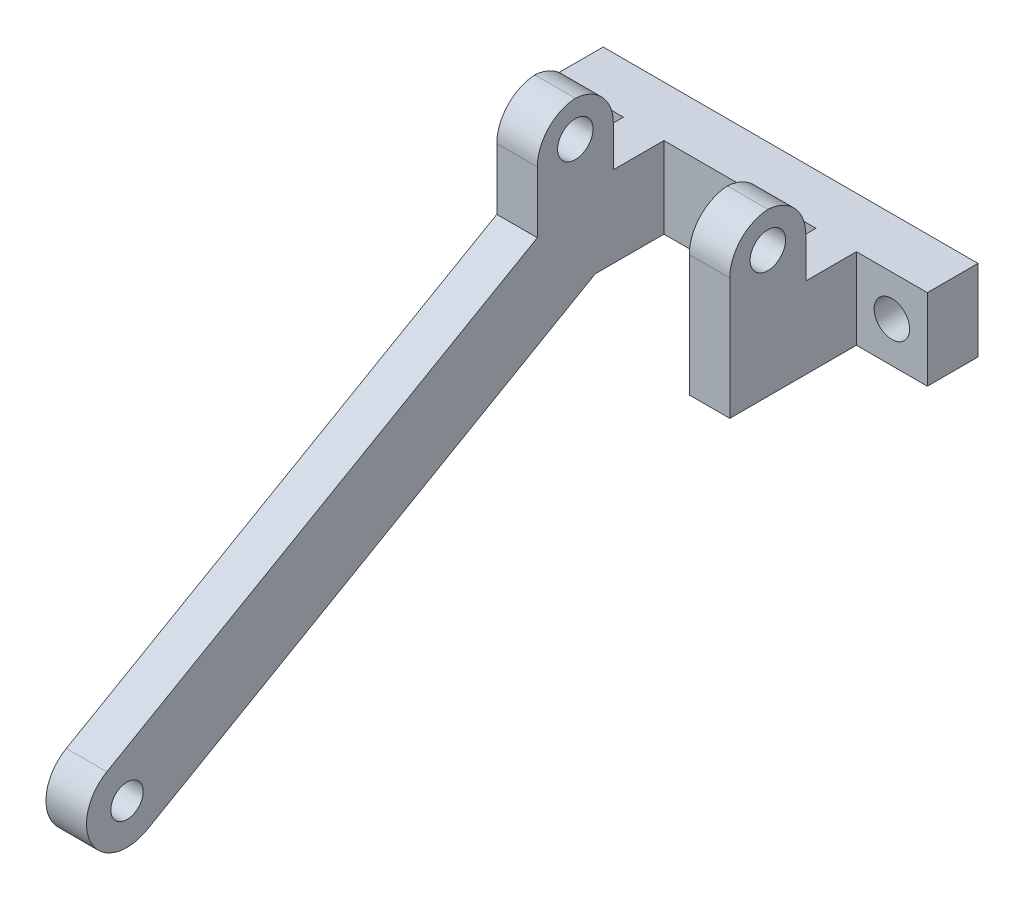
SolidWorks part; units mm, degrees
ref_plane "Front Plane" through (0, 0, 0) normal (0, 0, 1) x (1, 0, 0)
ref_plane "Top Plane" through (0, 0, 0) normal (0, 1, 0) x (1, 0, 0)
ref_plane "Right Plane" through (0, 0, 0) normal (1, 0, 0) x (0, 0, -1)
sketch "Sketch1" plane through (0, 0, 0) normal (0, 0, 1) x (1, 0, 0)
  line L0 (15, 0) -> (-15, 0) construction
  line L1 (-18.5, 4) -> (18.5, 4)
  line L2 (-18.5, 4) -> (-18.5, -4)
  line L3 (-18.5, -4) -> (18.5, -4)
  line L4 (18.5, 4) -> (18.5, -4)
  line L5 (-18.5, 4) -> (18.5, -4) construction
  line L6 (-18.5, -4) -> (18.5, 4) construction
  line L7 (0, -4) -> (0, 4) construction
  circle A0 centre (-15, 0) radius 1.75
  circle A1 centre (15, 0) radius 1.75
  point P0 (0, 0)
  point P12 (0, 0)
  dimension "D3" = 3.5
  dimension "D1" = 37
  dimension "D2" = 8
  dimension "D4" = 15
extrude "Boss-Extrude1" add sketch "Sketch1" along normal blind 5
sketch "Sketch2" plane through (0, 0, 5) normal (0, 0, 1) x (1, 0, 0)
  line L0 (0, 4) -> (0, -4) construction
  line L1 (18.5, 4) -> (-18.5, 4) construction
  line L2 (-18.5, -4) -> (18.5, -4) construction
  line L3 (11.5, -4) -> (7.5, 4) construction
  line L4 (-11.5, 4) -> (-7.5, 4)
  line L5 (-11.5, 4) -> (-11.5, -4)
  line L6 (-11.5, -4) -> (-7.5, -4)
  line L7 (-7.5, 4) -> (-7.5, -4)
  line L8 (-11.5, 4) -> (-7.5, -4) construction
  line L9 (-11.5, -4) -> (-7.5, 4) construction
  line L10 (11.5, 4) -> (7.5, -4) construction
  line L11 (7.5, 4) -> (7.5, -4)
  line L12 (11.5, -4) -> (7.5, -4)
  line L13 (11.5, 4) -> (11.5, -4)
  line L14 (11.5, 4) -> (7.5, 4)
  point P6 (-9.5, 0)
  point P15 (9.5, 0)
  dimension "D1" = 7.5
  dimension "D2" = 4
extrude "Boss-Extrude2" add sketch "Sketch2" along normal blind 12.5
sketch "Sketch4" plane through (0, 4, 0) normal (0, 1, 0) x (1, 0, 0)
  line L0 (-7.5, -17.5) -> (-7.5, -5) construction
  line L1 (-11.5, -17.5) -> (-7.5, -17.5)
  line L2 (-11.5, -17.5) -> (-11.5, -10)
  line L3 (-11.5, -10) -> (-7.5, -10)
  line L4 (-7.5, -17.5) -> (-7.5, -10)
  line L5 (0, 0) -> (0, -5) construction
  line L6 (7.5, -5) -> (-7.5, -5) construction
  line L7 (7.5, -17.5) -> (7.5, -10)
  line L8 (11.5, -10) -> (7.5, -10)
  line L9 (11.5, -17.5) -> (11.5, -10)
  line L10 (11.5, -17.5) -> (7.5, -17.5)
  dimension "D1" = 7.5
extrude "Boss-Extrude3" add sketch "Sketch4" along normal blind 8
sketch "Sketch3" plane through (-11.5, 0, 0) normal (-1, 0, 0) x (0, 0, 1)
  line L0 (10, 8.5) -> (17.5, 8.5) construction
  line L4 (10, 12) -> (10, 4) construction
  line L5 (17.5, 12) -> (17.5, -4) construction
  line L6 (13.75, 8.5) -> (13.75, 12) construction
  line L7 (10, 12) -> (17.5, 12) construction
  circle A0 centre (13.75, 8.5) radius 1.75
  dimension "D1" = 3.5
  dimension "D2" = 8.5
extrude "Cut-Extrude1" cut sketch "Sketch3" against normal through all
fillet "Fillet1" radius 4 4 edges at (-9.5, 12, 10) (9.5, 12, 10) (9.5, 12, 17.5) (-9.5, 12, 17.5)
sketch "Sketch5" plane through (-7.5, 0, 0) normal (1, 0, 0) x (0, 0, -1)
  line L0 (-10, 8) -> (-10, 4) construction
  line L1 (-10, 6.5) -> (-13, 6.5)
  line L2 (-10, 6.5) -> (-10, 1.5)
  line L3 (-10, 1.5) -> (-13, 1.5)
  line L4 (-13, 6.5) -> (-13, 1.5)
  line L5 (-10, 4) -> (-5, 4) construction
  dimension "D1" = 3
  dimension "D2" = 5
  dimension "D3" = 2.5
extrude "Boss-Extrude4" [suppressed] add sketch "Sketch5" along normal up to next
sketch "Sketch6" plane through (-11.5, 0, 0) normal (-1, 0, 0) x (0, 0, 1)
  line L0 (56.0113, -29.4012) -> (11.7824, -4)
  line L1 (17.5, -4) -> (5, -4) construction
  line L2 (11.7824, -4) -> (17.5, 1.9418)
  line L3 (13.75, 8.5) -> (58.0033, -25.9326) construction
  line L4 (17.5, 1.9418) -> (59.9954, -22.4639)
  line L5 (59.9954, -22.4639) -> (56.0113, -29.4012) construction
  line L6 (13.75, 8.5) -> (13.75, -4) construction
  line L7 (17.5, 8) -> (17.5, -4) construction
  circle A0 centre (58.0033, -25.9326) radius 1.6
  arc A1 (56.0113, -29.4012) -> (59.9954, -22.4639) centre (58.0033, -25.9326) ccw
  dimension "D1" = 3.2
  dimension "D2" = 8
  dimension "D3" = 52.114
  dimension "D4" = 56.071
  dimension "D5" = 1.9676
extrude "Boss-Extrude5" add sketch "Sketch6" against normal up to surface (4 mm away) up to face at (-7.5, 6.75, 13.75)
equation "\"X-ROD-SPACING\"=45"
equation "\"Y-ROD-SPACING\"=75"
equation "\"Z-ROD-SPACING\"=17.5"
equation "\"Y-BED-OFFSET\"=2"
equation "\"Y-BED-ROD-INSET\"=3.5"
equation "\"Y-BED-SCREW-SPACING\"=209"
equation "\"Y-BED-SCREW-CUTOUT-SLOT-HEIGHT\"=2"
equation "\"T-SLOT-NUT-FILLET-RADIUS\"=0.5"
equation "\"T-SLOT-SCREW-SHAFT-RADIUS\"=1.55"
equation "\"T-SLOT-SCREW-SHAFT-CUTOUT-LENGTH\"=11"
equation "\"T-SLOT-NUT-DEPTH\"=3.5"
equation "\"T-SLOT-NUT-WIDTH\"=2.85"
equation "\"T-SLOT-NUT-END-DISTANCE\"=8"
equation "\"ACRYLIC-THICKNESS\"=10"
equation "\"ACRYLIC-THICKNESS2\"=4.5"
equation "\"ACRYLIC-TAB-CUTOUT-SIZE\"=\"ACRYLIC-THICKNESS\"+\"ACRYLIC-TAB-TOLERANCE\"*2"
equation "\"ACRYLIC-TAB-TOLERANCE\"=-.05"
equation "\"ACRYLIC-TAB-WIDTH\"=\"ACRYLIC-THICKNESS\""
equation "\"ACRYLIC-M3-HOLE\"=2.9"
equation "\"SMOOTHROD-CAP-SCREW-DISTANCE\"=20"
equation "\"FRAME-WIDTH-INNER\"=370"
equation "\"NEMA17-HOLE-SPACING\"=31"
equation "\"NEMA17-CENTRAL-CUTOUT\"=22.5"
equation "\"Z-BRACKET-REACH\"=57"
equation "\"Z-ROD-INSET\"=13.5"
equation "\"TOP-BRACKET-SPACING\"=40"
equation "\"SMOOTHROD-X-LENGTH\"=350"
equation "\"SMOOTHROD-Y-LENGTH\"=350"
equation "\"SMOOTHROD-Z-LENGTH\"=350"
equation "\"SMOOTHROD-TIGHTENING-HEADROOM\"=.25"
equation "\"LEADSCREW-Z-LENGTH\"=300"
equation "\"SCREW-LENGTH-FRAME\"=\"ACRYLIC-THICKNESS\" + 10"
equation "\"SCREW-LENGTH-MOTOR\"=\"ACRYLIC-THICKNESS\" + 5"
equation "\"SCREW-LENGTH-EXTRUDER\"=28"
equation "\"SCREW-HEAD-RADIUS\"=6"
equation "\"PRINTED-X-SMOOTHROD-DIAMETER\"=8.8"
equation "\"PRINTED-X-SMOOTHROD-CUTOUT\"=10"
equation "\"PRINTED-X-BASE-HEIGHT\"=10"
equation "\"PRINTED-LM8UU-CUTOUT-SIZE\"=15.5"
equation "\"PRINTED-LM8UU-CUTOUT-LENGTH\"=24.5"
equation "\"PRINTED-X-IDLER-HEIGHT\"=16"
equation "\"PSU-MOUNTING-WIDTH\"=95"
equation "\"PSU-MOUNTING-HEIGHT\"=177"
equation "\"Y-BELT-TO-ROD-DISTANCE\"=20"
equation "\"SPOOL-HOLDER-ROD-SPACING\"=150"
equation "\"ACRYLIC-X-CARRIAGE-WIDTH\"=55"
equation "\"ACRYLIC-X-CARRIAGE-HEIGHT\"=75"
equation "\"ACRYLIC-X-CARRIAGE-LM8UU-CUTOUT-WIDTH\"=24.25"
equation "\"ACRYLIC-X-CARRIAGE-LM8UU-CUTOUT-HEIGHT\"=11.0"
equation "\"ACRYLIC-X-CARRIAGE-SCREW-SPACING-X\"=15"
equation "\"ACRYLIC-X-CARRIAGE-SCREW-SPACING-Y\"=33"
equation "\"ACRYLIC-X-CARRIAGE-CENTER-TAB-SPACING\"=14"
equation "\"ACRYLIC-X-CARRIAGE-EXTRUDER-OFFSET\"=26"
equation "\"ACRYLIC-X-CARRIAGE-EXTRUDER-ANGLE\"=90"
equation "\"ACRYLIC-X-CARRIAGE-EXTRUDER-SHELF-DEPTH\"=\"ACRYLIC-X-CARRIAGE-EXTRUDER-OFFSET\" + 28"
equation "\"ACRYLIC-X-CARRIAGE-EXTRUDER-BRACE-SPACING\"=23"
equation "\"ACRYLIC-X-CARRIAGE-EXTRUDER-BRACE-TAB-OFFSET\"=20"
equation "\"ACRYLIC-X-CARRIAGE-EXTRUDER-BRACE-HEIGHT\"=35"
equation "\"ACRYLIC-X-CARRIAGE-EXTRUDER-BRACE-SCREW-SPACING\"=22"
equation "\"ACRYLIC-X-CARRIAGE-DUAL-WIDTH-MULTIPLIER\"=1.65"
equation "\"ACRYLIC-X-CARRIAGE-DUAL-HOTEND-SPACING\"=42"
equation "\"ACRYLIC-X-CARRIAGE-DUAL-WIDTH\"=75"
equation "\"ACRYLIC-X-CARRIAGE-DUAL-HOTEND-SEPARATION\"=36"
equation "\"ACRYLIC-X-CARRIAGE-DUAL-MOUNT-PLATE-DEPTH\"=75"
equation "\"ACRYLIC-X-CARRIAGE-DUAL-MOUNT-BRACE-WIDTH\"=33"
equation "\"ACRYLIC-X-CARRIAGE-DUAL-MOUNT-SCREW-WIDTH\"=40"
equation "\"D3@Sketch1\"=3.5"
equation "\"PRINTED-M3-HOLE\"=3.5"
equation "\"BLOWER-FAN-WIDTH\"=15"
equation "\"D1@Sketch2\"=\"BLOWER-FAN-WIDTH\"/2"
